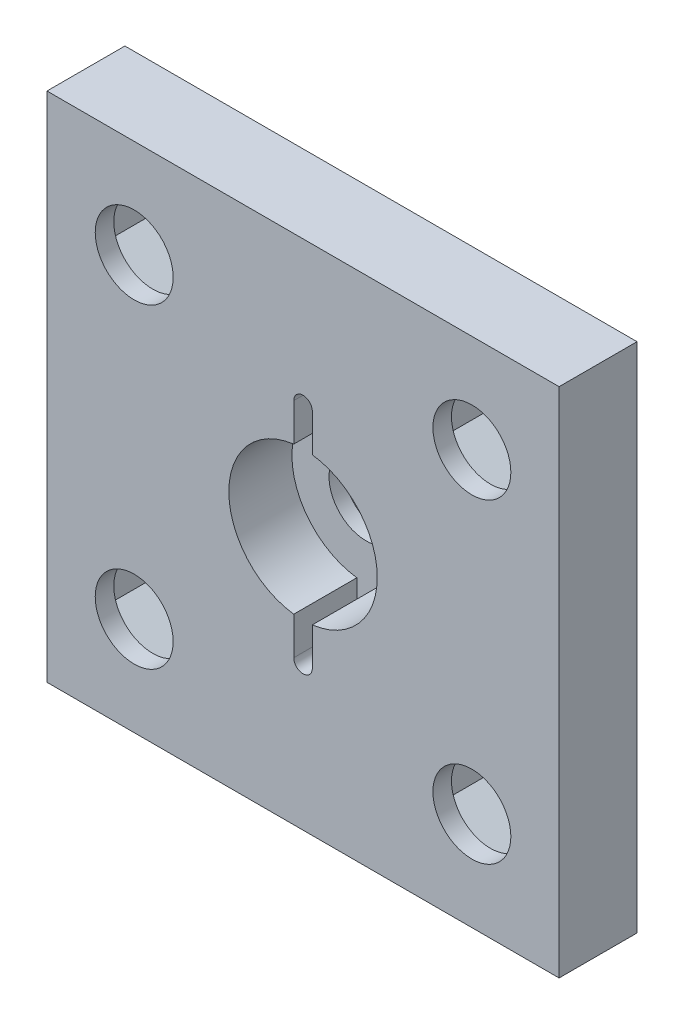
SolidWorks part; units mm, degrees
ref_plane "Front Plane" through (0, 0, 0) normal (0, 0, 1) x (1, 0, 0)
ref_plane "Top Plane" through (0, 0, 0) normal (0, 1, 0) x (1, 0, 0)
ref_plane "Right Plane" through (0, 0, 0) normal (1, 0, 0) x (0, 0, -1)
sketch "Sketch1" plane through (0, 0, 0) normal (0, 0, 1) x (1, 0, 0)
  line L0 (-8.89, 10.795) -> (8.89, 10.795) construction
  line L1 (17.526, 17.526) -> (-17.526, 17.526)
  line L2 (17.526, 17.526) -> (17.526, -17.526)
  line L3 (17.526, -17.526) -> (-17.526, -17.526)
  line L4 (-17.526, 17.526) -> (-17.526, -17.526)
  line L5 (17.526, 17.526) -> (-17.526, -17.526) construction
  line L6 (17.526, -17.526) -> (-17.526, 17.526) construction
  line L7 (0, 10.795) -> (0, -10.795) construction
  line L8 (-8.89, -10.795) -> (8.89, -10.795) construction
  circle A0 centre (-11.557, 10.795) radius 2.667
  circle A1 centre (11.557, 10.795) radius 2.667
  circle A2 centre (11.557, -10.795) radius 2.667
  circle A3 centre (-11.557, -10.795) radius 2.667
  point P0 (0, 0)
  point P18 (5.6883, -12.4589)
  point P19 (7.0449, -12.4589)
  point P20 (8.3046, -23.3305)
  point P21 (0, 11.8444)
  point P22 (0, 0)
  dimension "D3" = 5.334
  dimension "D4" = 16.256
  dimension "D5" = 17.78
  dimension "D1" = 35.052
  dimension "D2" = 35.052
extrude "Boss-Extrude1" add sketch "Sketch1" along normal blind 5.334
sketch "Sketch2" plane through (0, 0, 0) normal (0, 0, -1) x (-1, 0, 0)
  line L1 (-11.557, 5.9557) -> (-7.366, 8.3753)
  line L2 (-7.366, 8.3753) -> (-7.366, 13.2147)
  line L3 (-7.366, 13.2147) -> (-11.557, 15.6343)
  line L4 (-11.557, 15.6343) -> (-15.748, 13.2147)
  line L5 (-15.748, 13.2147) -> (-15.748, 8.3753)
  line L6 (-15.748, 8.3753) -> (-11.557, 5.9557)
  line L7 (-11.557, -15.6343) -> (-7.366, -13.2147)
  line L8 (-7.366, -13.2147) -> (-7.366, -8.3753)
  line L9 (-7.366, -8.3753) -> (-11.557, -5.9557)
  line L10 (-11.557, -5.9557) -> (-15.748, -8.3753)
  line L11 (-15.748, -8.3753) -> (-15.748, -13.2147)
  line L12 (-15.748, -13.2147) -> (-11.557, -15.6343)
  line L13 (11.557, -15.6343) -> (15.748, -13.2147)
  line L14 (15.748, -13.2147) -> (15.748, -8.3753)
  line L15 (15.748, -8.3753) -> (11.557, -5.9557)
  line L16 (11.557, -5.9557) -> (7.366, -8.3753)
  line L17 (7.366, -8.3753) -> (7.366, -13.2147)
  line L18 (7.366, -13.2147) -> (11.557, -15.6343)
  line L19 (11.557, 5.9557) -> (15.748, 8.3753)
  line L20 (15.748, 8.3753) -> (15.748, 13.2147)
  line L21 (15.748, 13.2147) -> (11.557, 15.6343)
  line L22 (11.557, 15.6343) -> (7.366, 13.2147)
  line L23 (7.366, 13.2147) -> (7.366, 8.3753)
  line L24 (7.366, 8.3753) -> (11.557, 5.9557)
  circle A0 centre (-11.557, 10.795) radius 4.191 construction
  circle A1 centre (-11.557, -10.795) radius 4.191 construction
  circle A2 centre (11.557, -10.795) radius 4.191 construction
  circle A3 centre (11.557, 10.795) radius 4.191 construction
  point P28 (-7.366, 10.795)
  dimension "D1" = 8.382
extrude "Cut-Extrude1" cut sketch "Sketch2" against normal offset from surface (4.064 mm away) 1.27 up to face at (0, 0, 5.334)
sketch "Sketch3" plane through (0, 0, 5.334) normal (0, 0, 1) x (1, 0, 0)
  circle A0 centre (0, 0) radius 5.08
  dimension "D1" = 10.16
extrude "Cut-Extrude2" cut sketch "Sketch3" against normal blind 4.318
sketch "Sketch4" plane through (0, 0, 5.334) normal (0, 0, 1) x (1, 0, 0)
  line L0 (0, -7.62) -> (0, 7.62) construction
  line L1 (-0.635, -7.62) -> (-0.635, 7.62)
  line L2 (0.635, -7.62) -> (0.635, 7.62)
  arc A0 (-0.635, -7.62) -> (0.635, -7.62) centre (0, -7.62) ccw
  arc A1 (0.635, 7.62) -> (-0.635, 7.62) centre (0, 7.62) ccw
  point P2 (0, 0)
  dimension "D1" = 1.27
  dimension "D2" = 15.24
extrude "Cut-Extrude3" cut sketch "Sketch4" against normal blind 4.318
sketch "Sketch5" plane through (0, 0, 1.016) normal (0, 0, 1) x (1, 0, 0)
  circle A0 centre (0, 0) radius 2.54
  dimension "D1" = 5.08
extrude "Cut-Extrude4" cut sketch "Sketch5" against normal through all
